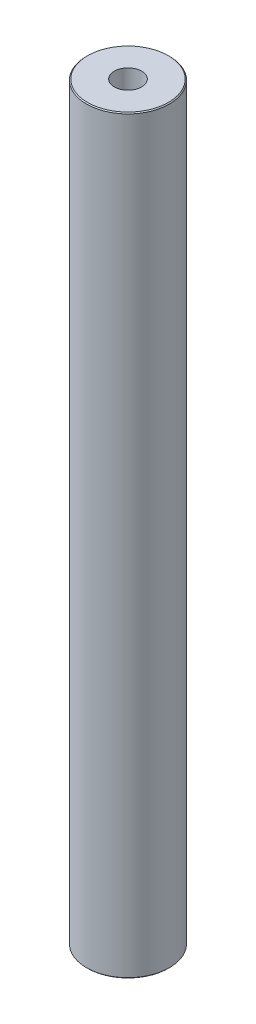
SolidWorks part; units mm, degrees
ref_plane "Front Plane" through (0, 0, 0) normal (0, 0, 1) x (1, 0, 0)
ref_plane "Top Plane" through (0, 0, 0) normal (0, 1, 0) x (1, 0, 0)
ref_plane "Right Plane" through (0, 0, 0) normal (1, 0, 0) x (0, 0, -1)
sketch "Sketch1" plane through (0, 0, 0) normal (0, 1, 0) x (1, 0, 0)
  circle A0 centre (0, 0) radius 12.5
  dimension "SHAFT_OD" = 25
extrude "Boss-Extrude1" add sketch "Sketch1" along normal blind 226.2314
sketch "Sketch2" plane through (0, 0, 0) normal (0, 1, 0) x (1, 0, 0)
  circle A0 centre (0, 0) radius 4.1321
  dimension "BORE_D" = 8.2642
extrude "Cut-Extrude1" cut sketch "Sketch2" along normal through all
chamfer "Chamfer1" distance 0.2899 angle 45.165 2 edges at (0, 226.2314, 12.5) (0, 0, 12.5) first distance on face at (0, 226.2314, 12.5) first distance on face at (0, 0, 4.1321)
